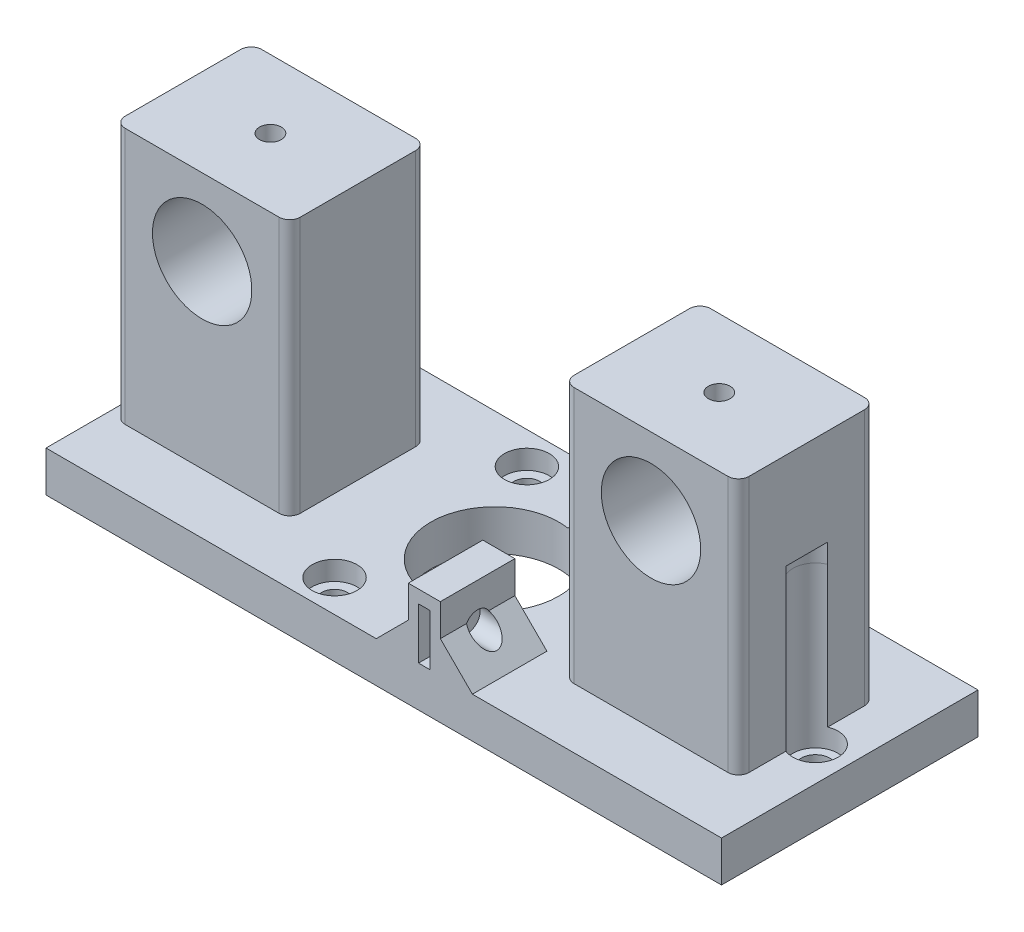
SolidWorks part; units mm, degrees
ref_plane "Front Plane" through (0, 0, 0) normal (0, 0, 1) x (1, 0, 0)
ref_plane "Top Plane" through (0, 0, 0) normal (0, 1, 0) x (1, 0, 0)
ref_plane "Right Plane" through (0, 0, 0) normal (1, 0, 0) x (0, 0, -1)
sketch "Sketch1" plane through (0, 0, 0) normal (0, 1, 0) x (1, 0, 0)
  line L0 (0, -30) -> (15, -30) construction
  line L1 (-50, -40) -> (50, -40)
  line L2 (-50, -40) -> (-50, 40)
  line L3 (-50, 40) -> (50, 40)
  line L4 (50, -40) -> (50, 40)
  line L5 (-50, -40) -> (50, 40) construction
  line L6 (-50, 40) -> (50, -40) construction
  line L7 (0, 0) -> (0, 40) construction
  line L9 (23, -11) -> (47, -11) construction
  line L10 (23, -11) -> (23, -29) construction
  line L11 (23, -29) -> (47, -29) construction
  line L12 (47, -11) -> (47, -29) construction
  line L13 (23, -11) -> (47, -29) construction
  line L14 (23, -29) -> (47, -11) construction
  circle A3 centre (0, -20) radius 10
  circle A4 centre (23, -29) radius 1.65
  circle A5 centre (47, -11) radius 1.65
  circle A6 centre (23, -11) radius 1.65
  circle A7 centre (47, -29) radius 1.65
  circle A8 centre (-23, -29) radius 1.65
  circle A9 centre (-47, -29) radius 1.65
  circle A10 centre (-47, -11) radius 1.65
  circle A11 centre (-23, -11) radius 1.65
  point P0 (0, 0)
  point P17 (35, -20)
  dimension "D6" = 20
  dimension "D1" = 15
  dimension "D3" = 80
  dimension "D7" = 24
  dimension "D8" = 18
  dimension "D9" = 100
  dimension "D10" = 35
extrude "Boss-Extrude1" add sketch "Sketch1" along normal blind 6.35
sketch "Sketch3" plane through (0, 6.35, 0) normal (0, 1, 0) x (1, 0, 0)
  line L0 (0, -20) -> (38.2541, 18.2541) construction
  line L1 (-50, -40) -> (50, -40) construction
  line L2 (-10, -20) -> (-10, -35) construction
  line L3 (0, -20) -> (-10, -20) construction
  circle A3 centre (50, -20) radius 2
  circle A5 centre (0, -20) radius 10 construction
  circle A6 centre (-10, -35) radius 2
  circle A8 centre (-10, -5) radius 2
  circle A10 centre (0, -20) radius 10 construction
  dimension "D1" = 45
  dimension "D2" = 15
extrude "Cut-Extrude5" cut sketch "Sketch3" against normal through all
sketch "Sketch5" plane through (0, 6.35, 0) normal (0, 1, 0) x (1, 0, 0)
  line L0 (50, -22) -> (50, -40)
  line L1 (50, 40) -> (55.3511, 40)
  line L2 (50, 40) -> (50, -18)
  line L3 (50, -40) -> (55.3511, -40)
  line L4 (55.3511, 40) -> (55.3511, -40)
  arc A0 (50, -22) -> (50, -18) centre (50, -20) ccw
extrude "Boss-Extrude2" add sketch "Sketch5" against normal up to surface (6.35 mm away) up to face at (16.3333, 0, 6.6667)
sketch "Sketch6" plane through (0, 6.35, 0) normal (0, 1, 0) x (1, 0, 0)
  line L0 (55.3511, -40) -> (55.3511, 40) construction
  line L1 (-50, 40) -> (55.3511, 40)
  line L2 (-50, 40) -> (-50, 0)
  line L3 (-50, 0) -> (55.3511, 0)
  line L4 (55.3511, 40) -> (55.3511, 0)
extrude "Cut-Extrude6" cut sketch "Sketch6" against normal through all
sketch "Sketch7" plane through (0, 6.35, 0) normal (0, 1, 0) x (1, 0, 0)
  circle A0 centre (-10, -5) radius 3.5
  circle A1 centre (-10, -35) radius 3.5
  circle A2 centre (50, -20) radius 3.5
extrude "Cut-Extrude7" cut sketch "Sketch7" against normal blind 3
sketch "Sketch8" plane through (0, 6.35, 0) normal (0, 1, 0) x (1, 0, 0)
  line L0 (-47, -29) -> (-23, -11) construction
  line L1 (-47, -11) -> (-23, -29) construction
  line L2 (0, 0) -> (0, -10) construction
  line L3 (-47, -9.35) -> (-23, -9.35)
  line L4 (-21.35, -11) -> (-21.35, -29)
  line L5 (-48.65, -11) -> (-48.65, -29)
  line L6 (-47, -30.65) -> (-23, -30.65)
  line L7 (21.35, -11) -> (21.35, -29)
  line L8 (47, -30.65) -> (23, -30.65)
  line L9 (48.65, -11) -> (48.65, -29)
  line L10 (47, -9.35) -> (23, -9.35)
  circle A0 centre (0, -20) radius 10 construction
  circle A1 centre (-47, -11) radius 1.65 construction
  circle A2 centre (-23, -11) radius 1.65 construction
  circle A3 centre (-23, -29) radius 1.65 construction
  circle A4 centre (-47, -29) radius 1.65 construction
  arc A5 (-47, -9.35) -> (-48.65, -11) centre (-47, -11) ccw
  arc A6 (-21.35, -11) -> (-23, -9.35) centre (-23, -11) ccw
  arc A7 (-23, -30.65) -> (-21.35, -29) centre (-23, -29) ccw
  arc A8 (-48.65, -29) -> (-47, -30.65) centre (-47, -29) ccw
  arc A9 (21.35, -11) -> (23, -9.35) centre (23, -11) cw
  arc A10 (48.65, -29) -> (47, -30.65) centre (47, -29) cw
  arc A11 (23, -30.65) -> (21.35, -29) centre (23, -29) cw
  arc A12 (47, -9.35) -> (48.65, -11) centre (47, -11) cw
extrude "Boss-Extrude4" add sketch "Sketch8" along normal blind 40 and the other way up to surface (6.35 mm away) other way up to face at (2.6756, 0, 20)
sketch "Sketch9" plane through (0, 6.35, 0) normal (0, 1, 0) x (1, 0, 0)
  circle A0 centre (50, -20) radius 3.4977
extrude "Cut-Extrude8" cut sketch "Sketch9" along normal blind 25
sketch "Sketch10" plane through (0, 3.35, 0) normal (0, 1, 0) x (1, 0, 0)
  circle A0 centre (50, -20) radius 2
  circle A1 centre (50, -20) radius 3.53
extrude "Cut-Extrude9" cut sketch "Sketch10" along normal blind 25
sketch "Sketch12" plane through (0, 0, 0) normal (0, -1, 0) x (1, 0, 0)
  circle A0 centre (50, 20) radius 2.2385
extrude "Cut-Extrude10" cut sketch "Sketch12" against normal blind 25
sketch "Sketch13" plane through (0, 0, 30.65) normal (0, 0, 1) x (1, 0, 0)
  line L0 (35, 46.35) -> (35, 6.35) construction
  line L1 (0, 0) -> (0, 6.35) construction
  line L2 (-50, 6.35) -> (55.3511, 6.35) construction
  line L3 (23, 46.35) -> (47, 46.35) construction
  circle A0 centre (35, 34.35) radius 7.75
  circle A1 centre (-35, 34.35) radius 7.75
  dimension "D1" = 12
extrude "Cut-Extrude11" cut sketch "Sketch13" against normal blind 25
sketch "Sketch14" plane through (0, 46.35, 0) normal (0, 1, 0) x (1, 0, 0)
  line L0 (47, -11) -> (23, -29) construction
  line L1 (0, 0) -> (0, -6.4322) construction
  circle A0 centre (35, -20) radius 1.7
  circle A1 centre (-35, -20) radius 1.7
extrude "Cut-Extrude12" cut sketch "Sketch14" against normal blind 10
sketch "Sketch15" plane through (0, 6.35, 0) normal (0, 1, 0) x (1, 0, 0)
  line L0 (0, 0) -> (0, -40) construction
  line L1 (-50, -40) -> (55.3511, -40) construction
  line L2 (0, 0) -> (-5.48, 0)
  line L3 (-50, 0) -> (55.3511, 0) construction
  line L4 (-5.48, 0) -> (-5.48, -9)
  dimension "D1" = 9
sketch "Sketch16" plane through (0, 6.35, 0) normal (0, 1, 0) x (1, 0, 0)
  line L0 (0, -20) -> (-9, -20) construction
  line L1 (0, 0) -> (0, -40) construction
  line L2 (0, -20) -> (9, -20) construction
  line L3 (9, -20) -> (9, 0) construction
  line L4 (-50, 0) -> (55.3511, 0) construction
  line L5 (11.5, -28.3785) -> (11.5, -40)
  line L6 (6.5, -11.6215) -> (8.1, -11.6215)
  line L7 (6.5, -11.6215) -> (6.5, 0)
  line L8 (6.5, 0) -> (8.1, 0)
  line L9 (11.5, -11.6215) -> (11.5, 0)
  line L10 (6.5, -11.6215) -> (11.5, 0) construction
  line L11 (6.5, 0) -> (11.5, -11.6215) construction
  line L12 (6.5, -40) -> (8.1, -40)
  line L13 (6.5, -28.3785) -> (6.5, -40)
  line L14 (6.5, -28.3785) -> (8.1, -28.3785)
  line L15 (9.9, -28.3785) -> (9.9, -40)
  line L17 (8.1, -11.6215) -> (8.1, 0)
  line L19 (9.9, -11.6215) -> (9.9, 0)
  line L20 (8.1, -28.3785) -> (8.1, -40)
  line L21 (9.9, -11.6215) -> (11.5, -11.6215)
  line L22 (9.9, 0) -> (11.5, 0)
  line L23 (9.9, -28.3785) -> (11.5, -28.3785)
  line L24 (9.9, -40) -> (11.5, -40)
  point P4 (9, -5.8108)
  dimension "D1" = 9
  dimension "D2" = 9
  dimension "D3" = 5
  dimension "D4" = 1.8
  dimension "D5" = 0.9
extrude "Boss-Extrude5" add sketch "Sketch16" along normal blind 8
chamfer "Chamfer1" distance 5 angle 45 2 edges at (11.5, 6.35, 34.1892) (11.5, 6.35, 5.8108)
chamfer "Chamfer2" distance 5 angle 45 2 edges at (6.5, 6.35, 34.1892) (6.5, 6.35, 5.8108)
sketch "Sketch17" plane through (11.5, 0, 0) normal (1, 0, 0) x (0, 0, -1)
  line L0 (-5.8108, 14.35) -> (-5.8108, 10.35) construction
  line L1 (-11.6215, 14.35) -> (0, 14.35) construction
  line L2 (-20, 6.35) -> (-20, 14.35) construction
  line L3 (0, 6.35) -> (-40, 6.35) construction
  circle A0 centre (-5.8108, 10.35) radius 2
  circle A1 centre (-34.1892, 10.35) radius 2
  dimension "D2" = 4
  dimension "D1" = 4
extrude "Cut-Extrude13" cut sketch "Sketch17" against normal up to surface (1.6 mm away) and the other way blind 8 up to face at (9.9, 10.35, 5.8108)
sketch "Sketch18" plane through (0, 14.35, 0) normal (0, 1, 0) x (1, 0, 0)
  line L1 (6.5, 0) -> (11.5, 0)
  line L2 (6.5, 0) -> (6.5, -11.6215)
  line L3 (6.5, -11.6215) -> (11.5, -11.6215)
  line L4 (11.5, 0) -> (11.5, -11.6215)
  line L5 (6.5, -28.3785) -> (11.5, -28.3785)
  line L6 (6.5, -28.3785) -> (6.5, -40)
  line L7 (6.5, -40) -> (11.5, -40)
  line L8 (11.5, -28.3785) -> (11.5, -40)
extrude "Boss-Extrude6" add sketch "Sketch18" along normal blind 2
